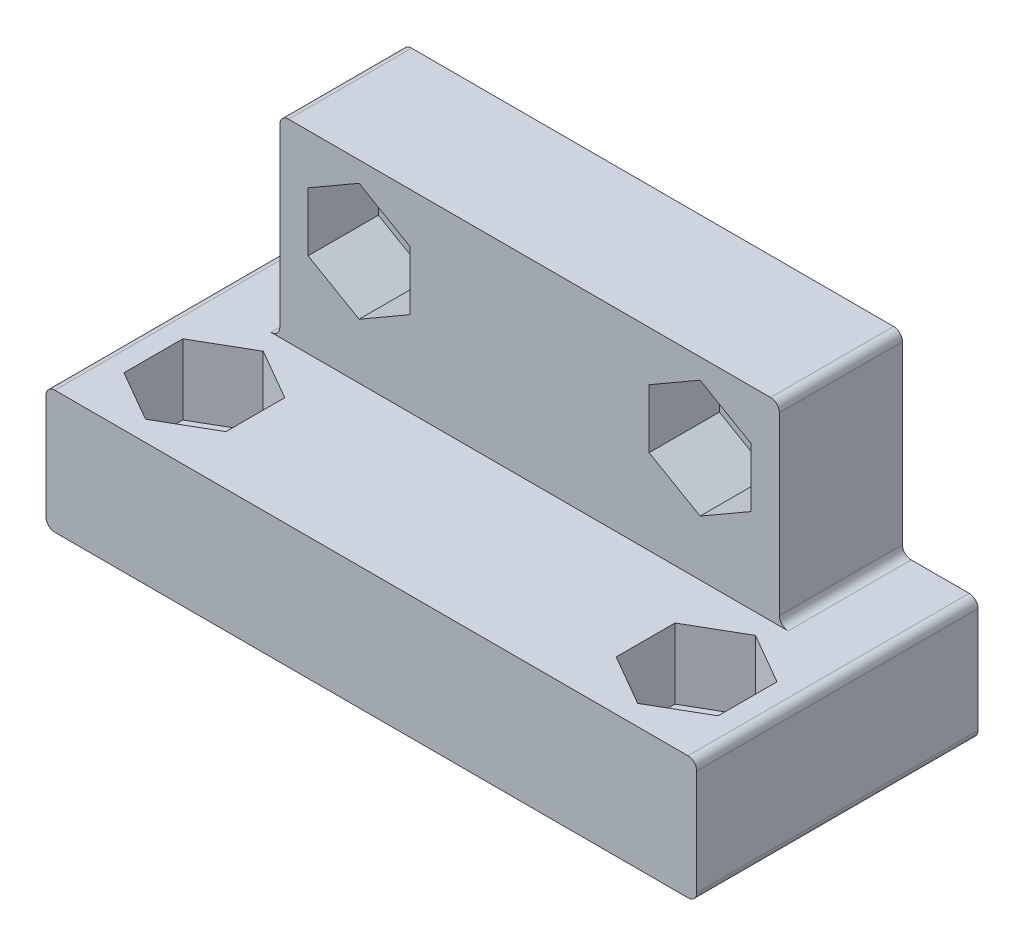
SolidWorks part; units mm, degrees
ref_plane "Front Plane" through (0, 0, 0) normal (0, 0, 1) x (1, 0, 0)
ref_plane "Top Plane" through (0, 0, 0) normal (0, 1, 0) x (1, 0, 0)
ref_plane "Right Plane" through (0, 0, 0) normal (1, 0, 0) x (0, 0, -1)
sketch "Sketch1" plane through (0, 0, 0) normal (0, 0, 1) x (1, 0, 0)
  line L29 (4.3, 7.5) -> (4.3, 17.5)
  line L30 (36.52, 7) -> (33.22, 7)
  line L32 (36.52, 0) -> (0.5, 0)
  line L34 (3.8, 7) -> (0.5, 7)
  line L35 (4.8, 18) -> (32.22, 18)
  line L36 (0, 6.5) -> (0, 0.5)
  line L37 (37.02, 0.5) -> (37.02, 6.5)
  line L38 (32.72, 7.5) -> (32.72, 17.5)
  arc A4 (0.5, 0) -> (0, 0.5) centre (0.5, 0.5) cw
  circle A12 centre (8.81, 13.5) radius 1.65
  circle A13 centre (28.21, 13.5) radius 1.65
  arc A14 (37.02, 6.5) -> (36.52, 7) centre (36.52, 6.5) ccw
  arc A15 (36.52, 0) -> (37.02, 0.5) centre (36.52, 0.5) ccw
  arc A16 (0.5, 7) -> (0, 6.5) centre (0.5, 6.5) ccw
  arc A17 (4.3, 7.5) -> (3.8, 7) centre (3.8, 7.5) cw
  arc A18 (4.3, 17.5) -> (4.8, 18) centre (4.8, 17.5) cw
  arc A19 (32.72, 17.5) -> (32.22, 18) centre (32.22, 17.5) ccw
  arc A20 (32.72, 7.5) -> (33.22, 7) centre (33.22, 7.5) ccw
extrude "Boss-Extrude1" add sketch "Sketch1" along normal blind 16
sketch "Sketch2" plane through (0, 0, 16) normal (0, 0, 1) x (1, 0, 0)
  line L0 (33.22, 7) -> (3.8, 7)
  line L5 (4.3, 18) -> (32.72, 18)
  line L9 (4.3, 18) -> (4.3, 7.5)
  line L10 (32.72, 18) -> (32.72, 7.5)
  arc A0 (3.8, 7) -> (4.3, 7.5) centre (3.8, 7.5) ccw
  arc A1 (32.72, 7.5) -> (33.22, 7) centre (33.22, 7.5) ccw
extrude "Cut-Extrude1" cut sketch "Sketch2" against normal offset from surface (9 mm away) 7 up to face at (10.46, 13.5, 0)
sketch "Sketch3" plane through (0, 0, 7) normal (0, 0, 1) x (1, 0, 0)
  line L0 (8.81, 10.1514) -> (11.71, 11.8257)
  line L1 (11.71, 11.8257) -> (11.71, 15.1743)
  line L2 (11.71, 15.1743) -> (8.81, 16.8486)
  line L3 (8.81, 16.8486) -> (5.91, 15.1743)
  line L4 (5.91, 15.1743) -> (5.91, 11.8257)
  line L5 (5.91, 11.8257) -> (8.81, 10.1514)
  line L6 (28.21, 10.1514) -> (31.11, 11.8257)
  line L7 (31.11, 11.8257) -> (31.11, 15.1743)
  line L8 (31.11, 15.1743) -> (28.21, 16.8486)
  line L9 (28.21, 16.8486) -> (25.31, 15.1743)
  line L10 (25.31, 15.1743) -> (25.31, 11.8257)
  line L11 (25.31, 11.8257) -> (28.21, 10.1514)
  circle A0 centre (8.81, 13.5) radius 2.9 construction
  circle A1 centre (28.21, 13.5) radius 2.9 construction
extrude "Cut-Extrude2" cut sketch "Sketch3" against normal offset from surface (4 mm away) 3 up to face at (10.46, 13.5, 0)
sketch "Sketch4" plane through (0, 7, 0) normal (0, 1, 0) x (1, 0, 0)
  circle A6 centre (32.51, -11.5) radius 1.65
  circle A7 centre (4.51, -11.5) radius 1.65
extrude "Cut-Extrude3" cut sketch "Sketch4" against normal up to surface (7 mm away) up to face at (18.51, 0, 8)
sketch "Sketch5" plane through (0, 7, 0) normal (0, 1, 0) x (1, 0, 0)
  line L0 (32.51, -14.8486) -> (35.41, -13.1743)
  line L1 (35.41, -13.1743) -> (35.41, -9.8257)
  line L2 (35.41, -9.8257) -> (32.51, -8.1514)
  line L3 (32.51, -8.1514) -> (29.61, -9.8257)
  line L4 (29.61, -9.8257) -> (29.61, -13.1743)
  line L5 (29.61, -13.1743) -> (32.51, -14.8486)
  line L6 (4.51, -14.8486) -> (7.41, -13.1743)
  line L7 (7.41, -13.1743) -> (7.41, -9.8257)
  line L8 (7.41, -9.8257) -> (4.51, -8.1514)
  line L9 (4.51, -8.1514) -> (1.61, -9.8257)
  line L10 (1.61, -9.8257) -> (1.61, -13.1743)
  line L11 (1.61, -13.1743) -> (4.51, -14.8486)
  circle A0 centre (32.51, -11.5) radius 2.9 construction
  circle A1 centre (4.51, -11.5) radius 2.9 construction
extrude "Cut-Extrude4" cut sketch "Sketch5" against normal offset from surface (4 mm away) 3 up to face at (30.86, 0, 11.5)
